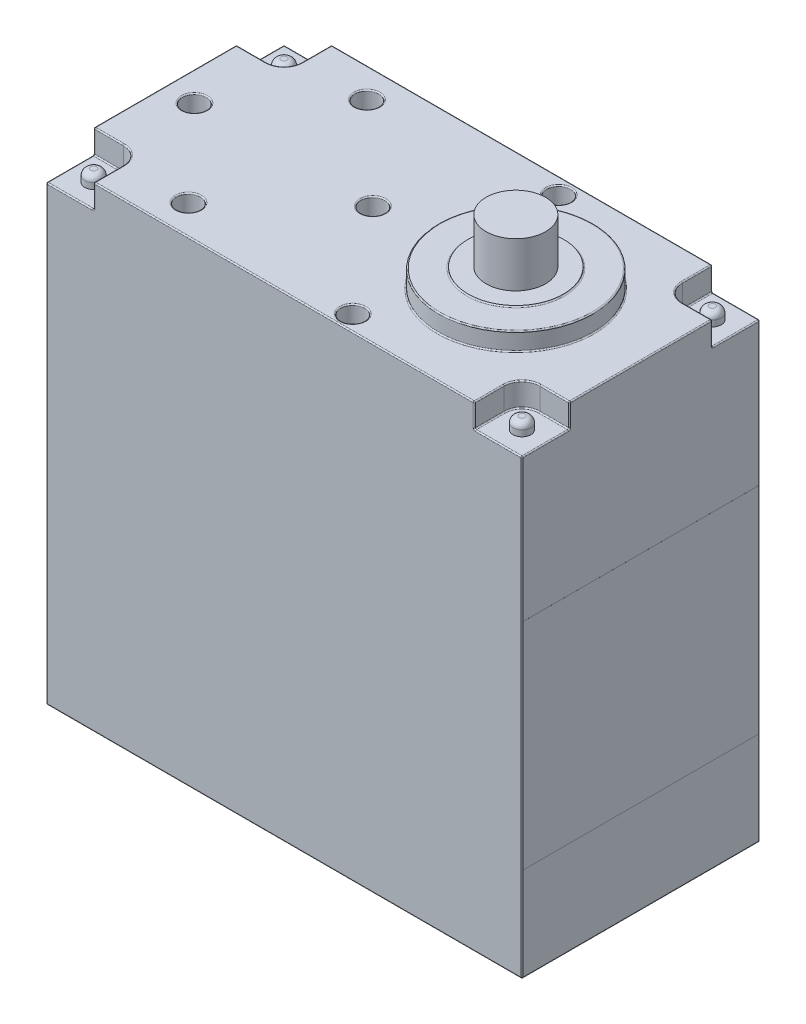
SolidWorks part; units mm, degrees
ref_plane "Ön Düzlem" through (0, 0, 0) normal (0, 0, 1) x (1, 0, 0)
ref_plane "Üst Düzlem" through (0, 0, 0) normal (0, 1, 0) x (1, 0, 0)
ref_plane "Sağ Düzlem" through (0, 0, 0) normal (1, 0, 0) x (0, 0, -1)
sketch "Çizim1" plane through (0, 0, 0) normal (0, 0, 1) x (1, 0, 0)
  line L0 (0, 0) -> (40, 0)
  line L1 (40, 0) -> (40, 40)
  line L2 (40, 40) -> (0, 40)
  line L3 (0, 40) -> (0, 0)
  dimension "D1" = 40
  dimension "D2" = 40
extrude "Yükseklik-Ekstrüzyon1" add sketch "Çizim1" along normal blind 20
sketch "Çizim2" plane through (0, 40, 0) normal (0, 1, 0) x (1, 0, 0)
  line L2 (0, 0) -> (4, 0)
  line L4 (0, 0) -> (0, -4)
  line L5 (0, -4) -> (2.5, -4)
  line L7 (4, 0) -> (4, -2.5)
  line L8 (0, -20) -> (4, -20)
  line L9 (0, -20) -> (0, -16)
  line L10 (0, -16) -> (2.5, -16)
  line L11 (4, -20) -> (4, -17.5)
  line L12 (40, 0) -> (36, 0)
  line L13 (40, 0) -> (40, -4)
  line L14 (40, -4) -> (37.5, -4)
  line L15 (36, 0) -> (36, -2.5)
  line L16 (40, -20) -> (36, -20)
  line L17 (40, -20) -> (40, -16)
  line L18 (40, -16) -> (37.5, -16)
  line L19 (36, -20) -> (36, -17.5)
  arc A0 (37.5, -4) -> (36, -2.5) centre (37.5, -2.5) cw
  arc A1 (37.5, -16) -> (36, -17.5) centre (37.5, -17.5) ccw
  arc A2 (2.5, -16) -> (4, -17.5) centre (2.5, -17.5) cw
  arc A3 (2.5, -4) -> (4, -2.5) centre (2.5, -2.5) ccw
  circle A4 centre (2.463, -10) radius 1
  circle A7 centre (9.463, -17.5) radius 1
  circle A8 centre (9.463, -2.5) radius 1
  circle A9 centre (24.463, -1.3797) radius 1
  circle A10 centre (24.463, -18.6922) radius 1
  circle A11 centre (17.463, -10) radius 1
  point P28 (4, -4)
  dimension "D2" = 1.5
  dimension "D3" = 2
  dimension "D5" = 2
  dimension "D6" = 2
  dimension "D1" = 4
  dimension "D4" = 7
  dimension "D7" = 15
  dimension "D9" = 7
extrude "Kes-Ekstrüzyon1" cut sketch "Çizim2" against normal blind 2
sketch "Çizim3" plane through (0, 40, 0) normal (0, 1, 0) x (1, 0, 0)
  circle A0 centre (29.483, -10) radius 6.5
  circle A1 centre (2.463, -10) radius 1 construction
  dimension "D1" = 13
  dimension "D2" = 27.02
extrude "Yükseklik-Ekstrüzyon2" add sketch "Çizim3" along normal blind 1.5
sketch "Çizim4" plane through (0, 41.5, 0) normal (0, 1, 0) x (1, 0, 0)
  circle A0 centre (29.483, -10) radius 4
  dimension "D1" = 8
extrude "Yükseklik-Ekstrüzyon3" add sketch "Çizim4" along normal blind 0.1
sketch "Çizim5" plane through (0, 41.6, 0) normal (0, 1, 0) x (1, 0, 0)
  circle A1 centre (29.483, -10) radius 2.5
  dimension "D1" = 5
extrude "Yükseklik-Ekstrüzyon4" add sketch "Çizim5" along normal blind 3.8
fillet "Radyus2" radius 0.1 54 edges at (1.25, 40, 4) (3.5607, 40, 3.5607) (4, 40, 1.25) (36, 40, 1.25) (36.4393, 40, 3.5607) (38.75, 40, 4) (38.75, 40, 16) (36.4393, 40, 16.4393) (36, 40, 18.75) (4, 40, 18.75) (3.5607, 40, 16.4393) (1.25, 40, 16) (0, 0, 10) (0, 39, 4) (0, 40, 10) (0, 39, 16) (4, 38, 1.25) (3.5607, 38, 3.5607) (1.25, 38, 4) (0, 38, 2) (29.483, 41.5, 16.5) (29.483, 41.5, 14) (1.25, 38, 16) (3.5607, 38, 16.4393) (4, 38, 18.75) (0, 38, 18) (36, 38, 18.75) (36.4393, 38, 16.4393) (38.75, 38, 16) (38.75, 38, 4) (36.4393, 38, 3.5607) (36, 38, 1.25) (4, 39, 0) (2, 38, 0) (0, 19, 0) (20, 0, 0) (38, 38, 0) (36, 39, 0) (20, 40, 0) (40, 19, 0) (40, 0, 10) (40, 38, 18) (40, 39, 16) (40, 40, 10) (40, 39, 4) (40, 38, 2) (20, 40, 20) (36, 39, 20) (38, 38, 20) (40, 19, 20) (20, 0, 20) (0, 19, 20) (2, 38, 20) (4, 39, 20)
fillet "Radyus3" radius 0.1 1 edges at (2.463, 40, 11)
fillet "Radyus4" radius 0.1 6 edges at (24.463, 40, 2.3797) (9.463, 40, 18.5) (9.463, 40, 3.5) (17.463, 40, 11) (24.463, 40, 19.6922) (29.483, 40, 3.5)
sketch "Çizim7" plane through (0, 38, 0) normal (0, 1, 0) x (1, 0, 0)
  circle A0 centre (2, -18) radius 0.75
  dimension "D1" = 1.5
extrude "Yükseklik-Ekstrüzyon5" add sketch "Çizim7" along normal blind 1
fillet "Radyus5" radius 0.5 1 edges at (2, 39, 18.75)
pattern_linear "LÇoğaltma1" count 2 spacing 36 along (1, 0, 0) count 2 spacing 16 along (0, 0, -1) of "Yükseklik-Ekstrüzyon5", "Radyus5"
sketch "Çizim8" plane through (0, 0, 0) normal (0, -1, 0) x (1, 0, 0)
  line L5 (0.1, 0.1) -> (39.9, 0.1) construction
  circle A0 centre (1.6, 17.5) radius 1
  circle A1 centre (16.6, 17.5) radius 1
  circle A2 centre (16.6, 2.5) radius 1
  circle A3 centre (1.6, 2.5) radius 1
  circle A4 centre (36.6, 17.5) radius 1
  circle A5 centre (36.6, 2.5) radius 1
  dimension "D1" = 2
  dimension "D3" = 15
  dimension "D2" = 2
  dimension "D5" = 15
  dimension "D7" = 2.4
  dimension "D4" = 2
extrude "Kes-Ekstrüzyon2" cut sketch "Çizim8" against normal blind 2
sketch "Çizim9" plane through (0, 0, 0) normal (0, -1, 0) x (1, 0, 0)
  circle A0 centre (29.1, 10) radius 6.5
  dimension "D1" = 13
extrude "Yükseklik-Ekstrüzyon6" add sketch "Çizim9" along normal blind 1.5
sketch "Çizim10" plane through (0, -1.5, 0) normal (0, -1, 0) x (1, 0, 0)
  circle A0 centre (29.1, 10) radius 4
  dimension "D1" = 8
extrude "Yükseklik-Ekstrüzyon7" add sketch "Çizim10" along normal blind 0.1
sketch "Çizim11" plane through (0, -1.6, 0) normal (0, -1, 0) x (1, 0, 0)
  circle A0 centre (29.1, 10) radius 4
extrude "Yükseklik-Ekstrüzyon8" add sketch "Çizim11" along normal blind 4.1
sketch "Çizim13" plane through (0, 0, 0) normal (0, 0, -1) x (-1, 0, 0)
  line L1 (-39.9, 37.9) -> (-39.9, 0.1) construction
  line L2 (-39.9, 25.99) -> (-0.1, 25.99)
  line L3 (-0.1, 0.1) -> (-0.1, 37.9) construction
  line L4 (-0.1, 25.99) -> (-0.1, 7.9)
  line L5 (-0.1, 7.9) -> (-39.9, 7.9)
  line L6 (-39.9, 7.9) -> (-39.9, 25.99)
sketch "Çizim15" plane through (0, 0, 20) normal (0, 0, 1) x (1, 0, 0)
  line L0 (0.1, 25.99) -> (39.9, 25.99)
  line L1 (39.9, 25.99) -> (39.9, 7.9)
  line L2 (39.9, 7.9) -> (0.1, 7.9)
  line L3 (0.1, 7.9) -> (0.1, 25.99)
  line L4 (79.9596, 114.1998) -> (387.9596, 114.1998) construction
  line L5 (0.1, 25.9904) -> (0.1329, 25.9904)
sketch "Çizim16" plane through (0, 0, 0) normal (-1, 0, 0) x (0, 0, 1)
  line L0 (0.1, 25.9906) -> (19.9, 25.9906)
  line L5 (19.9, 25.9906) -> (19.9, 7.9006)
  line L7 (0.1, 7.9006) -> (19.9, 7.9006)
  line L8 (0.1, 37.9) -> (0.1, 0.1) construction
  line L11 (19.9, 0.1) -> (19.9, 37.9) construction
  line L12 (0.1, 25.9906) -> (0.1, 7.9006)
  dimension "D1" = 18.09
extrude "Yükseklik-Ekstrüzyon10" add sketch "Çizim13" along normal blind 0.001
extrude "Yükseklik-Ekstrüzyon11" add sketch "Çizim16" along normal blind 0.001
sketch "Çizim17" plane through (40, 0, 0) normal (1, 0, 0) x (0, 0, -1)
  line L0 (-19.9, 25.9814) -> (-0.1, 25.9814)
  line L1 (-19.9, 37.9) -> (-19.9, 0.1) construction
  line L2 (-0.1, 0.1) -> (-0.1, 37.9) construction
  line L3 (-0.1, 25.9814) -> (-0.1, 7.8914)
  line L4 (-0.1, 7.8914) -> (-19.9, 7.8914)
  line L5 (-19.9, 7.8914) -> (-19.9, 25.9814)
extrude "Yükseklik-Ekstrüzyon12" add sketch "Çizim17" along normal blind 0.001
